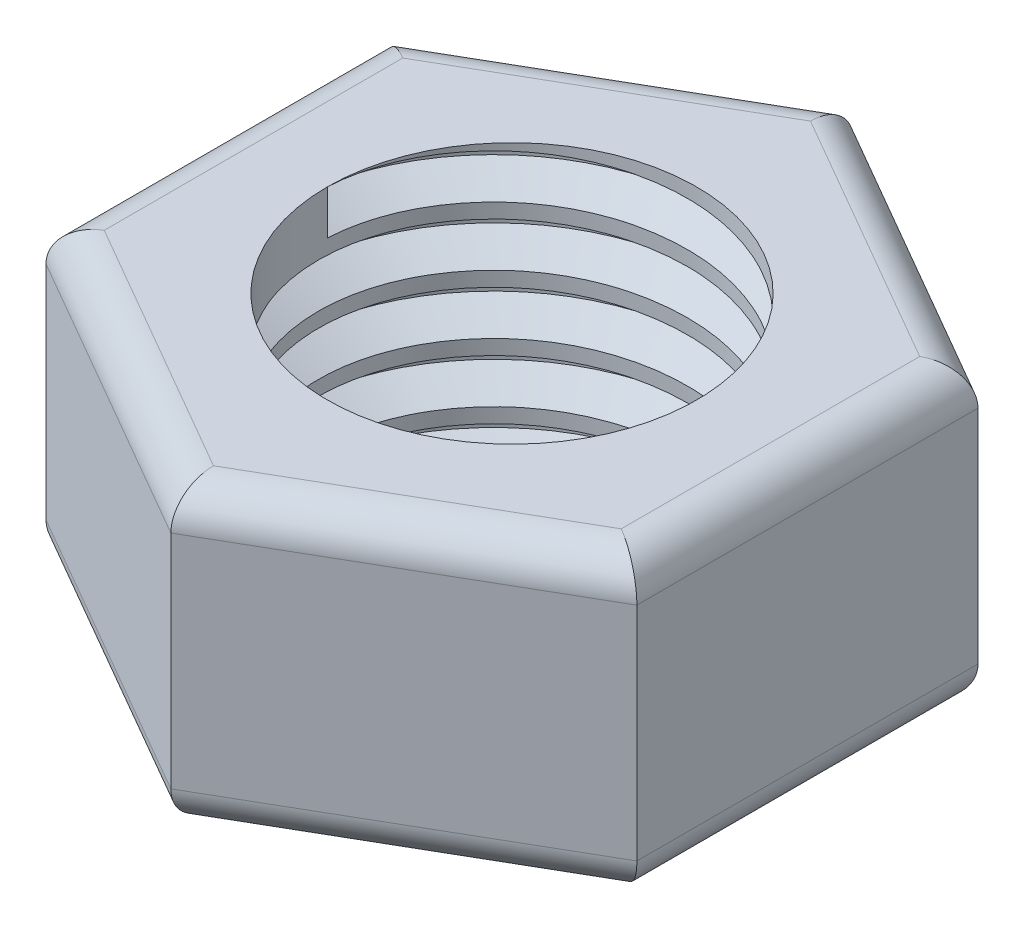
SolidWorks part; units mm, degrees
ref_plane "Front Plane" through (0, 0, 0) normal (0, 0, 1) x (1, 0, 0)
ref_plane "Top Plane" through (0, 0, 0) normal (0, 1, 0) x (1, 0, 0)
ref_plane "Right Plane" through (0, 0, 0) normal (1, 0, 0) x (0, 0, -1)
sketch "Sketch1" plane through (0, 0, 0) normal (0, 1, 0) x (1, 0, 0)
  line L1 (0, 4.6188) -> (-4, 2.3094)
  line L2 (-4, 2.3094) -> (-4, -2.3094)
  line L3 (-4, -2.3094) -> (0, -4.6188)
  line L4 (0, -4.6188) -> (4, -2.3094)
  line L5 (4, -2.3094) -> (4, 2.3094)
  line L6 (4, 2.3094) -> (0, 4.6188)
  circle A0 centre (0, 0) radius 4 construction
  circle A1 centre (0, 0) radius 2.5
  dimension "D3" = 5
  dimension "D1" = 8
  dimension "D2" = 4
extrude "Boss-Extrude1" add sketch "Sketch1" along normal blind 4
thread "Thread1" pitch 0.8 method cut profile "Thread Profile1" start angle 0, offset 0, length 4, pitch 0.8, diameter 5
ref_plane "Plane1" through (-2.5, 4, 0) normal (0, 0, 1) x (-1, 0, 0)
sketch "Thread Profile1" plane through (-2.5, 4, 0) normal (0, 0, 1) x (-1, 0, 0)
  line L0 (0, 0) -> (0, 0.8) construction
  line L1 (0, 0) -> (0.433, 0.25)
  line L2 (0.433, 0.25) -> (0.433, 0.35)
  line L3 (0.433, 0.35) -> (0, 0.6)
  line L4 (0.433, 0.3) -> (0, 0.3) construction
  line L11 (0, 0) -> (0, 0.6)
  point P2 (0, 0)
  dimension "Pitch" = 0.8
  dimension "Profile_Angle" = 60
  dimension "Profile_Land" = 0.1
  dimension "Profile_Height" = 0.433
fillet "Fillet1" radius 0.5 12 edges at (-4, 0, 0) (-2, 0, -3.4641) (2, 0, -3.4641) (4, 0, 0) (-2, 0, 3.4641) (2, 0, 3.4641) (-2, 4, 3.4641) (-4, 4, 0) (-2, 4, -3.4641) (2, 4, -3.4641) (4, 4, 0) (2, 4, 3.4641)
